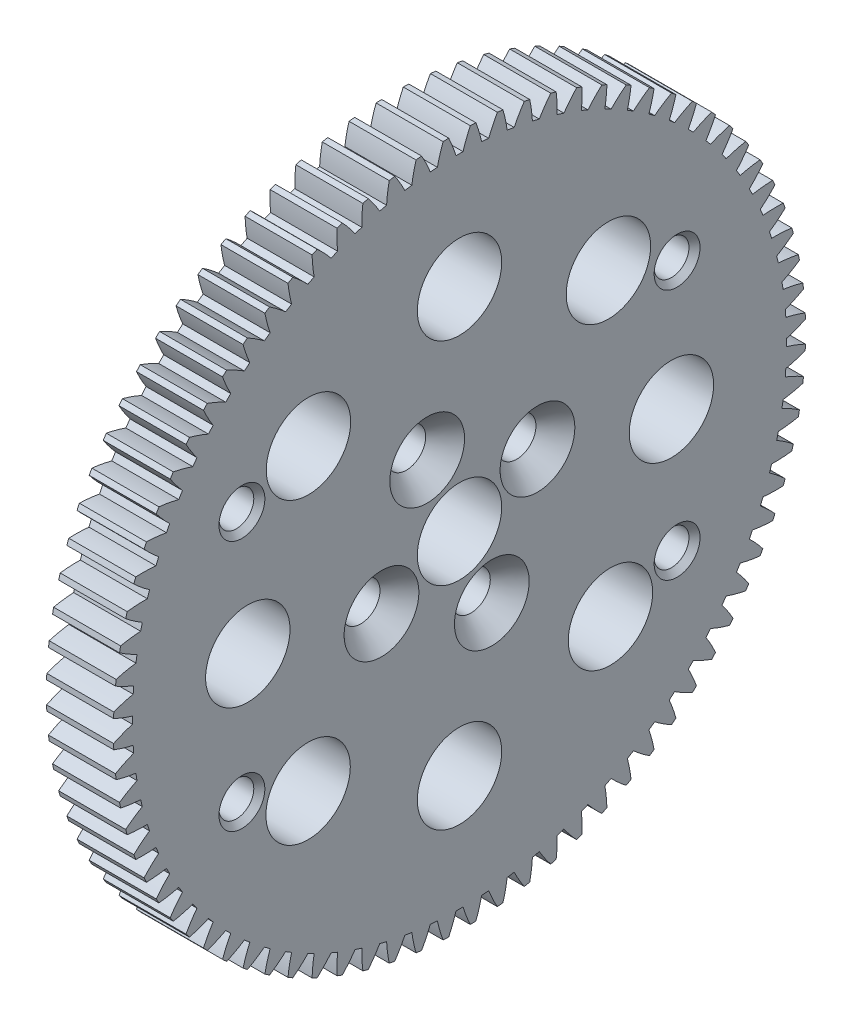
SolidWorks part; units mm, degrees
material "2024 Alloy"
ref_plane "Front Plane" through (0, 0, 0) normal (0, 0, 1) x (1, 0, 0)
ref_plane "Top Plane" through (0, 0, 0) normal (0, 1, 0) x (1, 0, 0)
ref_plane "Right Plane" through (0, 0, 0) normal (1, 0, 0) x (0, 0, -1)
ref_plane "Plane1" through (0, 0, 0) normal (-1, 0, 0) x (0, -1, 0)
ref_axis "Axis1" through (-3.4925, 0, 0) along (1, 0, 0)
sketch "Sketch1" plane through (0, 0, 0) normal (-1, 0, 0) x (0, -1, 0)
  line L0 (3.0615, 7.391) -> (-3.0615, -7.391) construction
  line L1 (7.391, -3.0615) -> (-7.391, 3.0615) construction
  circle A0 centre (0, 0) radius 4
  circle A1 centre (3.0615, 7.391) radius 1.75
  circle A2 centre (-20.084, 0) radius 4
  circle A3 centre (20.0633, 0) radius 4
  circle A4 centre (0, -20.084) radius 4
  circle A5 centre (0, 20.0633) radius 4
  circle A6 centre (-14.3663, -14.1126) radius 4
  circle A7 centre (14.142, -14.3069) radius 4
  circle A8 centre (14.1351, 14.3483) radius 4
  circle A9 centre (-14.1597, 14.315) radius 4
  circle A10 centre (-7.391, 3.0615) radius 1.75
  circle A11 centre (7.391, -3.0615) radius 1.75
  circle A12 centre (-3.0615, -7.391) radius 1.75
  arc A13 (-32.5405, -4.1179) -> (-30.6681, -4.5175) centre (-28.9403, 8.1654) ccw
  arc A14 (-30.6681, -4.5175) -> (-30.563, -5.1806) centre (0, 0) ccw
  arc A15 (-30.563, -5.1806) -> (-32.2203, -6.1392) centre (-25.0006, -16.7088) ccw
  arc A16 (-32.2203, -6.1392) -> (-32.1171, -6.6583) centre (0, 0) ccw
  arc A17 (-32.1171, -6.6583) -> (-30.2191, -6.9097) centre (-29.4917, 5.8696) ccw
  arc A18 (-30.2191, -6.9097) -> (-30.0624, -7.5626) centre (0, 0) ccw
  arc A19 (-30.0624, -7.5626) -> (-31.6393, -8.6483) centre (-23.6126, -18.6188) ccw
  arc A20 (-31.6393, -8.6483) -> (-31.4957, -9.1576) centre (0, 0) ccw
  arc A21 (-31.4957, -9.1576) -> (-29.5838, -9.2594) centre (-29.8613, 3.5376) ccw
  arc A22 (-29.5838, -9.2594) -> (-29.3763, -9.8979) centre (0, 0) ccw
  arc A23 (-29.3763, -9.8979) -> (-30.8633, -11.104) centre (-22.079, -20.414) ccw
  arc A24 (-30.8633, -11.104) -> (-30.6801, -11.6005) centre (0, 0) ccw
  arc A25 (-30.6801, -11.6005) -> (-28.7661, -11.552) centre (-30.0469, 1.1838) ccw
  arc A26 (-28.7661, -11.552) -> (-28.5092, -12.1723) centre (0, 0) ccw
  arc A27 (-28.5092, -12.1723) -> (-29.8969, -13.4913) centre (-20.4093, -22.0834) ccw
  arc A28 (-29.8969, -13.4913) -> (-29.6753, -13.9719) centre (0, 0) ccw
  arc A29 (-29.6753, -13.9719) -> (-27.7711, -13.7733) centre (-30.0471, -1.1773) ccw
  arc A30 (-27.7711, -13.7733) -> (-27.4663, -14.3715) centre (0, 0) ccw
  arc A31 (-27.4663, -14.3715) -> (-28.7462, -15.7954) centre (-18.6137, -23.6166) ccw
  arc A32 (-28.7462, -15.7954) -> (-28.4876, -16.2571) centre (0, 0) ccw
  arc A33 (-28.4876, -16.2571) -> (-26.6048, -15.9097) centre (-29.8621, -3.5311) ccw
  arc A34 (-26.6048, -15.9097) -> (-26.254, -16.4822) centre (0, 0) ccw
  arc A35 (-26.254, -16.4822) -> (-27.4183, -18.0021) centre (-16.7034, -25.0042) ccw
  arc A36 (-27.4183, -18.0021) -> (-27.1243, -18.4421) centre (0, 0) ccw
  arc A37 (-27.1243, -18.4421) -> (-25.2746, -17.9481) centre (-29.493, -5.8632) ccw
  arc A38 (-25.2746, -17.9481) -> (-24.8799, -18.4913) centre (0, 0) ccw
  arc A39 (-24.8799, -18.4913) -> (-25.9214, -20.0978) centre (-14.6901, -26.2377) ccw
  arc A40 (-25.9214, -20.0978) -> (-25.5937, -20.5134) centre (0, 0) ccw
  arc A41 (-25.5937, -20.5134) -> (-23.7885, -19.8758) centre (-28.9421, -8.1591) ccw
  arc A42 (-23.7885, -19.8758) -> (-23.3524, -20.3863) centre (0, 0) ccw
  arc A43 (-23.3524, -20.3863) -> (-24.2646, -22.0696) centre (-12.5862, -27.3094) ccw
  arc A44 (-24.2646, -22.0696) -> (-23.9054, -22.4582) centre (0, 0) ccw
  arc A45 (-23.9054, -22.4582) -> (-22.1557, -21.6809) centre (-28.2127, -10.4047) ccw
  arc A46 (-22.1557, -21.6809) -> (-21.6809, -22.1557) centre (0, 0) ccw
  arc A47 (-21.6809, -22.1557) -> (-22.4582, -23.9054) centre (-10.4047, -28.2127) ccw
  arc A48 (-22.4582, -23.9054) -> (-22.0696, -24.2646) centre (0, 0) ccw
  arc A49 (-22.0696, -24.2646) -> (-20.3863, -23.3524) centre (-27.3094, -12.5862) ccw
  arc A50 (-20.3863, -23.3524) -> (-19.8758, -23.7885) centre (0, 0) ccw
  arc A51 (-19.8758, -23.7885) -> (-20.5134, -25.5937) centre (-8.1591, -28.9421) ccw
  arc A52 (-20.5134, -25.5937) -> (-20.0978, -25.9214) centre (0, 0) ccw
  arc A53 (-20.0978, -25.9214) -> (-18.4913, -24.8799) centre (-26.2377, -14.6901) ccw
  arc A54 (-18.4913, -24.8799) -> (-17.9481, -25.2746) centre (0, 0) ccw
  arc A55 (-17.9481, -25.2746) -> (-18.4421, -27.1243) centre (-5.8632, -29.493) ccw
  arc A56 (-18.4421, -27.1243) -> (-18.0021, -27.4183) centre (0, 0) ccw
  arc A57 (-18.0021, -27.4183) -> (-16.4822, -26.254) centre (-25.0042, -16.7034) ccw
  arc A58 (-16.4822, -26.254) -> (-15.9097, -26.6048) centre (0, 0) ccw
  arc A59 (-15.9097, -26.6048) -> (-16.2571, -28.4876) centre (-3.5311, -29.8621) ccw
  arc A60 (-16.2571, -28.4876) -> (-15.7954, -28.7462) centre (0, 0) ccw
  arc A61 (-15.7954, -28.7462) -> (-14.3715, -27.4663) centre (-23.6166, -18.6137) ccw
  arc A62 (-14.3715, -27.4663) -> (-13.7733, -27.7711) centre (0, 0) ccw
  arc A63 (-13.7733, -27.7711) -> (-13.9719, -29.6753) centre (-1.1773, -30.0471) ccw
  arc A64 (-13.9719, -29.6753) -> (-13.4913, -29.8969) centre (0, 0) ccw
  arc A65 (-13.4913, -29.8969) -> (-12.1723, -28.5092) centre (-22.0834, -20.4093) ccw
  arc A66 (-12.1723, -28.5092) -> (-11.552, -28.7661) centre (0, 0) ccw
  arc A67 (-11.552, -28.7661) -> (-11.6005, -30.6801) centre (1.1838, -30.0469) ccw
  arc A68 (-11.6005, -30.6801) -> (-11.104, -30.8633) centre (0, 0) ccw
  arc A69 (-11.104, -30.8633) -> (-9.8979, -29.3763) centre (-20.414, -22.079) ccw
  arc A70 (-9.8979, -29.3763) -> (-9.2594, -29.5838) centre (0, 0) ccw
  arc A71 (-9.2594, -29.5838) -> (-9.1576, -31.4957) centre (3.5376, -29.8613) ccw
  arc A72 (-9.1576, -31.4957) -> (-8.6483, -31.6393) centre (0, 0) ccw
  arc A73 (-8.6483, -31.6393) -> (-7.5626, -30.0624) centre (-18.6188, -23.6126) ccw
  arc A74 (-7.5626, -30.0624) -> (-6.9097, -30.2191) centre (0, 0) ccw
  arc A75 (-6.9097, -30.2191) -> (-6.6583, -32.1171) centre (5.8696, -29.4917) ccw
  arc A76 (-6.6583, -32.1171) -> (-6.1392, -32.2203) centre (0, 0) ccw
  arc A77 (-6.1392, -32.2203) -> (-5.1806, -30.563) centre (-16.7088, -25.0006) ccw
  arc A78 (-5.1806, -30.563) -> (-4.5175, -30.6681) centre (0, 0) ccw
  arc A79 (-4.5175, -30.6681) -> (-4.1179, -32.5405) centre (8.1654, -28.9403) ccw
  arc A80 (-4.1179, -32.5405) -> (-3.5923, -32.6027) centre (0, 0) ccw
  arc A81 (-3.5923, -32.6027) -> (-2.7667, -30.8753) centre (-14.6958, -26.2345) ccw
  arc A82 (-2.7667, -30.8753) -> (-2.0973, -30.928) centre (0, 0) ccw
  arc A83 (-2.0973, -30.928) -> (-1.5521, -32.7633) centre (10.4109, -28.2104) ccw
  arc A84 (-1.5521, -32.7633) -> (-1.0233, -32.784) centre (0, 0) ccw
  arc A85 (-1.0233, -32.784) -> (-0.3357, -30.9972) centre (-12.5921, -27.3066) ccw
  arc A86 (-0.3357, -30.9972) -> (0.3357, -30.9972) centre (0, 0) ccw
  arc A87 (0.3357, -30.9972) -> (1.0233, -32.784) centre (12.5921, -27.3066) ccw
  arc A88 (1.0233, -32.784) -> (1.5521, -32.7633) centre (0, 0) ccw
  arc A89 (1.5521, -32.7633) -> (2.0973, -30.928) centre (-10.4109, -28.2104) ccw
  arc A90 (2.0973, -30.928) -> (2.7667, -30.8753) centre (0, 0) ccw
  arc A91 (2.7667, -30.8753) -> (3.5923, -32.6027) centre (14.6958, -26.2345) ccw
  arc A92 (3.5923, -32.6027) -> (4.1179, -32.5405) centre (0, 0) ccw
  arc A93 (4.1179, -32.5405) -> (4.5175, -30.6681) centre (-8.1654, -28.9403) ccw
  arc A94 (4.5175, -30.6681) -> (5.1806, -30.563) centre (0, 0) ccw
  arc A95 (5.1806, -30.563) -> (6.1392, -32.2203) centre (16.7088, -25.0006) ccw
  arc A96 (6.1392, -32.2203) -> (6.6583, -32.1171) centre (0, 0) ccw
  arc A97 (6.6583, -32.1171) -> (6.9097, -30.2191) centre (-5.8696, -29.4917) ccw
  arc A98 (6.9097, -30.2191) -> (7.5626, -30.0624) centre (0, 0) ccw
  arc A99 (7.5626, -30.0624) -> (8.6483, -31.6393) centre (18.6188, -23.6126) ccw
  arc A100 (8.6483, -31.6393) -> (9.1576, -31.4957) centre (0, 0) ccw
  arc A101 (9.1576, -31.4957) -> (9.2594, -29.5838) centre (-3.5376, -29.8613) ccw
  arc A102 (9.2594, -29.5838) -> (9.8979, -29.3763) centre (0, 0) ccw
  arc A103 (9.8979, -29.3763) -> (11.104, -30.8633) centre (20.414, -22.079) ccw
  arc A104 (11.104, -30.8633) -> (11.6005, -30.6801) centre (0, 0) ccw
  arc A105 (11.6005, -30.6801) -> (11.552, -28.7661) centre (-1.1838, -30.0469) ccw
  arc A106 (11.552, -28.7661) -> (12.1723, -28.5092) centre (0, 0) ccw
  arc A107 (12.1723, -28.5092) -> (13.4913, -29.8969) centre (22.0834, -20.4093) ccw
  arc A108 (13.4913, -29.8969) -> (13.9719, -29.6753) centre (0, 0) ccw
  arc A109 (13.9719, -29.6753) -> (13.7733, -27.7711) centre (1.1773, -30.0471) ccw
  arc A110 (13.7733, -27.7711) -> (14.3715, -27.4663) centre (0, 0) ccw
  arc A111 (14.3715, -27.4663) -> (15.7954, -28.7462) centre (23.6166, -18.6137) ccw
  arc A112 (15.7954, -28.7462) -> (16.2571, -28.4876) centre (0, 0) ccw
  arc A113 (16.2571, -28.4876) -> (15.9097, -26.6048) centre (3.5311, -29.8621) ccw
  arc A114 (15.9097, -26.6048) -> (16.4822, -26.254) centre (0, 0) ccw
  arc A115 (16.4822, -26.254) -> (18.0021, -27.4183) centre (25.0042, -16.7034) ccw
  arc A116 (18.0021, -27.4183) -> (18.4421, -27.1243) centre (0, 0) ccw
  arc A117 (18.4421, -27.1243) -> (17.9481, -25.2746) centre (5.8632, -29.493) ccw
  arc A118 (17.9481, -25.2746) -> (18.4913, -24.8799) centre (0, 0) ccw
  arc A119 (18.4913, -24.8799) -> (20.0978, -25.9214) centre (26.2377, -14.6901) ccw
  arc A120 (20.0978, -25.9214) -> (20.5134, -25.5937) centre (0, 0) ccw
  arc A121 (20.5134, -25.5937) -> (19.8758, -23.7885) centre (8.1591, -28.9421) ccw
  arc A122 (19.8758, -23.7885) -> (20.3863, -23.3524) centre (0, 0) ccw
  arc A123 (20.3863, -23.3524) -> (22.0696, -24.2646) centre (27.3094, -12.5862) ccw
  arc A124 (22.0696, -24.2646) -> (22.4582, -23.9054) centre (0, 0) ccw
  arc A125 (22.4582, -23.9054) -> (21.6809, -22.1557) centre (10.4047, -28.2127) ccw
  arc A126 (21.6809, -22.1557) -> (22.1557, -21.6809) centre (0, 0) ccw
  arc A127 (22.1557, -21.6809) -> (23.9054, -22.4582) centre (28.2127, -10.4047) ccw
  arc A128 (23.9054, -22.4582) -> (24.2646, -22.0696) centre (0, 0) ccw
  arc A129 (24.2646, -22.0696) -> (23.3524, -20.3863) centre (12.5862, -27.3094) ccw
  arc A130 (23.3524, -20.3863) -> (23.7885, -19.8758) centre (0, 0) ccw
  arc A131 (23.7885, -19.8758) -> (25.5937, -20.5134) centre (28.9421, -8.1591) ccw
  arc A132 (25.5937, -20.5134) -> (25.9214, -20.0978) centre (0, 0) ccw
  arc A133 (25.9214, -20.0978) -> (24.8799, -18.4913) centre (14.6901, -26.2377) ccw
  arc A134 (24.8799, -18.4913) -> (25.2746, -17.9481) centre (0, 0) ccw
  arc A135 (25.2746, -17.9481) -> (27.1243, -18.4421) centre (29.493, -5.8632) ccw
  arc A136 (27.1243, -18.4421) -> (27.4183, -18.0021) centre (0, 0) ccw
  arc A137 (27.4183, -18.0021) -> (26.254, -16.4822) centre (16.7034, -25.0042) ccw
  arc A138 (26.254, -16.4822) -> (26.6048, -15.9097) centre (0, 0) ccw
  arc A139 (26.6048, -15.9097) -> (28.4876, -16.2571) centre (29.8621, -3.5311) ccw
  arc A140 (28.4876, -16.2571) -> (28.7462, -15.7954) centre (0, 0) ccw
  arc A141 (28.7462, -15.7954) -> (27.4663, -14.3715) centre (18.6137, -23.6166) ccw
  arc A142 (27.4663, -14.3715) -> (27.7711, -13.7733) centre (0, 0) ccw
  arc A143 (27.7711, -13.7733) -> (29.6753, -13.9719) centre (30.0471, -1.1773) ccw
  arc A144 (29.6753, -13.9719) -> (29.8969, -13.4913) centre (0, 0) ccw
  arc A145 (29.8969, -13.4913) -> (28.5092, -12.1723) centre (20.4093, -22.0834) ccw
  arc A146 (28.5092, -12.1723) -> (28.7661, -11.552) centre (0, 0) ccw
  arc A147 (28.7661, -11.552) -> (30.6801, -11.6005) centre (30.0469, 1.1838) ccw
  arc A148 (30.6801, -11.6005) -> (30.8633, -11.104) centre (0, 0) ccw
  arc A149 (30.8633, -11.104) -> (29.3763, -9.8979) centre (22.079, -20.414) ccw
  arc A150 (29.3763, -9.8979) -> (29.5838, -9.2594) centre (0, 0) ccw
  arc A151 (29.5838, -9.2594) -> (31.4957, -9.1576) centre (29.8613, 3.5376) ccw
  arc A152 (31.4957, -9.1576) -> (31.6393, -8.6483) centre (0, 0) ccw
  arc A153 (31.6393, -8.6483) -> (30.0624, -7.5626) centre (23.6126, -18.6188) ccw
  arc A154 (30.0624, -7.5626) -> (30.2191, -6.9097) centre (0, 0) ccw
  arc A155 (30.2191, -6.9097) -> (32.1171, -6.6583) centre (29.4917, 5.8696) ccw
  arc A156 (32.1171, -6.6583) -> (32.2203, -6.1392) centre (0, 0) ccw
  arc A157 (32.2203, -6.1392) -> (30.563, -5.1806) centre (25.0006, -16.7088) ccw
  arc A158 (30.563, -5.1806) -> (30.6681, -4.5175) centre (0, 0) ccw
  arc A159 (30.6681, -4.5175) -> (32.5405, -4.1179) centre (28.9403, 8.1654) ccw
  arc A160 (32.5405, -4.1179) -> (32.6027, -3.5923) centre (0, 0) ccw
  arc A161 (32.6027, -3.5923) -> (30.8753, -2.7667) centre (26.2345, -14.6958) ccw
  arc A162 (30.8753, -2.7667) -> (30.928, -2.0973) centre (0, 0) ccw
  arc A163 (30.928, -2.0973) -> (32.7633, -1.5521) centre (28.2104, 10.4109) ccw
  arc A164 (32.7633, -1.5521) -> (32.784, -1.0233) centre (0, 0) ccw
  arc A165 (32.784, -1.0233) -> (30.9972, -0.3357) centre (27.3066, -12.5921) ccw
  arc A166 (30.9972, -0.3357) -> (30.9972, 0.3357) centre (0, 0) ccw
  arc A167 (30.9972, 0.3357) -> (32.784, 1.0233) centre (27.3066, 12.5921) ccw
  arc A168 (32.784, 1.0233) -> (32.7633, 1.5521) centre (0, 0) ccw
  arc A169 (32.7633, 1.5521) -> (30.928, 2.0973) centre (28.2104, -10.4109) ccw
  arc A170 (30.928, 2.0973) -> (30.8753, 2.7667) centre (0, 0) ccw
  arc A171 (30.8753, 2.7667) -> (32.6027, 3.5923) centre (26.2345, 14.6958) ccw
  arc A172 (32.6027, 3.5923) -> (32.5405, 4.1179) centre (0, 0) ccw
  arc A173 (32.5405, 4.1179) -> (30.6681, 4.5175) centre (28.9403, -8.1654) ccw
  arc A174 (30.6681, 4.5175) -> (30.563, 5.1806) centre (0, 0) ccw
  arc A175 (30.563, 5.1806) -> (32.2203, 6.1392) centre (25.0006, 16.7088) ccw
  arc A176 (32.2203, 6.1392) -> (32.1171, 6.6583) centre (0, 0) ccw
  arc A177 (32.1171, 6.6583) -> (30.2191, 6.9097) centre (29.4917, -5.8696) ccw
  arc A178 (30.2191, 6.9097) -> (30.0624, 7.5626) centre (0, 0) ccw
  arc A179 (30.0624, 7.5626) -> (31.6393, 8.6483) centre (23.6126, 18.6188) ccw
  arc A180 (31.6393, 8.6483) -> (31.4957, 9.1576) centre (0, 0) ccw
  arc A181 (31.4957, 9.1576) -> (29.5838, 9.2594) centre (29.8613, -3.5376) ccw
  arc A182 (29.5838, 9.2594) -> (29.3763, 9.8979) centre (0, 0) ccw
  arc A183 (29.3763, 9.8979) -> (30.8633, 11.104) centre (22.079, 20.414) ccw
  arc A184 (30.8633, 11.104) -> (30.6801, 11.6005) centre (0, 0) ccw
  arc A185 (30.6801, 11.6005) -> (28.7661, 11.552) centre (30.0469, -1.1838) ccw
  arc A186 (28.7661, 11.552) -> (28.5092, 12.1723) centre (0, 0) ccw
  arc A187 (28.5092, 12.1723) -> (29.8969, 13.4913) centre (20.4093, 22.0834) ccw
  arc A188 (29.8969, 13.4913) -> (29.6753, 13.9719) centre (0, 0) ccw
  arc A189 (29.6753, 13.9719) -> (27.7711, 13.7733) centre (30.0471, 1.1773) ccw
  arc A190 (27.7711, 13.7733) -> (27.4663, 14.3715) centre (0, 0) ccw
  arc A191 (27.4663, 14.3715) -> (28.7462, 15.7954) centre (18.6137, 23.6166) ccw
  arc A192 (28.7462, 15.7954) -> (28.4876, 16.2571) centre (0, 0) ccw
  arc A193 (28.4876, 16.2571) -> (26.6048, 15.9097) centre (29.8621, 3.5311) ccw
  arc A194 (26.6048, 15.9097) -> (26.254, 16.4822) centre (0, 0) ccw
  arc A195 (26.254, 16.4822) -> (27.4183, 18.0021) centre (16.7034, 25.0042) ccw
  arc A196 (27.4183, 18.0021) -> (27.1243, 18.4421) centre (0, 0) ccw
  arc A197 (27.1243, 18.4421) -> (25.2746, 17.9481) centre (29.493, 5.8632) ccw
  arc A198 (25.2746, 17.9481) -> (24.8799, 18.4913) centre (0, 0) ccw
  arc A199 (24.8799, 18.4913) -> (25.9214, 20.0978) centre (14.6901, 26.2377) ccw
  arc A200 (25.9214, 20.0978) -> (25.5937, 20.5134) centre (0, 0) ccw
  arc A201 (25.5937, 20.5134) -> (23.7885, 19.8758) centre (28.9421, 8.1591) ccw
  arc A202 (23.7885, 19.8758) -> (23.3524, 20.3863) centre (0, 0) ccw
  arc A203 (23.3524, 20.3863) -> (24.2646, 22.0696) centre (12.5862, 27.3094) ccw
  arc A204 (24.2646, 22.0696) -> (23.9054, 22.4582) centre (0, 0) ccw
  arc A205 (23.9054, 22.4582) -> (22.1557, 21.6809) centre (28.2127, 10.4047) ccw
  arc A206 (22.1557, 21.6809) -> (21.6809, 22.1557) centre (0, 0) ccw
  arc A207 (21.6809, 22.1557) -> (22.4582, 23.9054) centre (10.4047, 28.2127) ccw
  arc A208 (22.4582, 23.9054) -> (22.0696, 24.2646) centre (0, 0) ccw
  arc A209 (22.0696, 24.2646) -> (20.3863, 23.3524) centre (27.3094, 12.5862) ccw
  arc A210 (20.3863, 23.3524) -> (19.8758, 23.7885) centre (0, 0) ccw
  arc A211 (19.8758, 23.7885) -> (20.5134, 25.5937) centre (8.1591, 28.9421) ccw
  arc A212 (20.5134, 25.5937) -> (20.0978, 25.9214) centre (0, 0) ccw
  arc A213 (20.0978, 25.9214) -> (18.4913, 24.8799) centre (26.2377, 14.6901) ccw
  arc A214 (18.4913, 24.8799) -> (17.9481, 25.2746) centre (0, 0) ccw
  arc A215 (17.9481, 25.2746) -> (18.4421, 27.1243) centre (5.8632, 29.493) ccw
  arc A216 (18.4421, 27.1243) -> (18.0021, 27.4183) centre (0, 0) ccw
  arc A217 (18.0021, 27.4183) -> (16.4822, 26.254) centre (25.0042, 16.7034) ccw
  arc A218 (16.4822, 26.254) -> (15.9097, 26.6048) centre (0, 0) ccw
  arc A219 (15.9097, 26.6048) -> (16.2571, 28.4876) centre (3.5311, 29.8621) ccw
  arc A220 (16.2571, 28.4876) -> (15.7954, 28.7462) centre (0, 0) ccw
  arc A221 (15.7954, 28.7462) -> (14.3715, 27.4663) centre (23.6166, 18.6137) ccw
  arc A222 (14.3715, 27.4663) -> (13.7733, 27.7711) centre (0, 0) ccw
  arc A223 (13.7733, 27.7711) -> (13.9719, 29.6753) centre (1.1773, 30.0471) ccw
  arc A224 (13.9719, 29.6753) -> (13.4913, 29.8969) centre (0, 0) ccw
  arc A225 (13.4913, 29.8969) -> (12.1723, 28.5092) centre (22.0834, 20.4093) ccw
  arc A226 (12.1723, 28.5092) -> (11.552, 28.7661) centre (0, 0) ccw
  arc A227 (11.552, 28.7661) -> (11.6005, 30.6801) centre (-1.1838, 30.0469) ccw
  arc A228 (11.6005, 30.6801) -> (11.104, 30.8633) centre (0, 0) ccw
  arc A229 (11.104, 30.8633) -> (9.8979, 29.3763) centre (20.414, 22.079) ccw
  arc A230 (9.8979, 29.3763) -> (9.2594, 29.5838) centre (0, 0) ccw
  arc A231 (9.2594, 29.5838) -> (9.1576, 31.4957) centre (-3.5376, 29.8613) ccw
  arc A232 (9.1576, 31.4957) -> (8.6483, 31.6393) centre (0, 0) ccw
  arc A233 (8.6483, 31.6393) -> (7.5626, 30.0624) centre (18.6188, 23.6126) ccw
  arc A234 (7.5626, 30.0624) -> (6.9097, 30.2191) centre (0, 0) ccw
  arc A235 (6.9097, 30.2191) -> (6.6583, 32.1171) centre (-5.8696, 29.4917) ccw
  arc A236 (6.6583, 32.1171) -> (6.1392, 32.2203) centre (0, 0) ccw
  arc A237 (6.1392, 32.2203) -> (5.1806, 30.563) centre (16.7088, 25.0006) ccw
  arc A238 (5.1806, 30.563) -> (4.5175, 30.6681) centre (0, 0) ccw
  arc A239 (4.5175, 30.6681) -> (4.1179, 32.5405) centre (-8.1654, 28.9403) ccw
  arc A240 (4.1179, 32.5405) -> (3.5923, 32.6027) centre (0, 0) ccw
  arc A241 (3.5923, 32.6027) -> (2.7667, 30.8753) centre (14.6958, 26.2345) ccw
  arc A242 (2.7667, 30.8753) -> (2.0973, 30.928) centre (0, 0) ccw
  arc A243 (2.0973, 30.928) -> (1.5521, 32.7633) centre (-10.4109, 28.2104) ccw
  arc A244 (1.5521, 32.7633) -> (1.0233, 32.784) centre (0, 0) ccw
  arc A245 (1.0233, 32.784) -> (0.3357, 30.9972) centre (12.5921, 27.3066) ccw
  arc A246 (0.3357, 30.9972) -> (-0.3357, 30.9972) centre (0, 0) ccw
  arc A247 (-0.3357, 30.9972) -> (-1.0233, 32.784) centre (-12.5921, 27.3066) ccw
  arc A248 (-1.0233, 32.784) -> (-1.5521, 32.7633) centre (0, 0) ccw
  arc A249 (-1.5521, 32.7633) -> (-2.0973, 30.928) centre (10.4109, 28.2104) ccw
  arc A250 (-2.0973, 30.928) -> (-2.7667, 30.8753) centre (0, 0) ccw
  arc A251 (-2.7667, 30.8753) -> (-3.5923, 32.6027) centre (-14.6958, 26.2345) ccw
  arc A252 (-3.5923, 32.6027) -> (-4.1179, 32.5405) centre (0, 0) ccw
  arc A253 (-4.1179, 32.5405) -> (-4.5175, 30.6681) centre (8.1654, 28.9403) ccw
  arc A254 (-4.5175, 30.6681) -> (-5.1806, 30.563) centre (0, 0) ccw
  arc A255 (-5.1806, 30.563) -> (-6.1392, 32.2203) centre (-16.7088, 25.0006) ccw
  arc A256 (-6.1392, 32.2203) -> (-6.6583, 32.1171) centre (0, 0) ccw
  arc A257 (-6.6583, 32.1171) -> (-6.9097, 30.2191) centre (5.8696, 29.4917) ccw
  arc A258 (-6.9097, 30.2191) -> (-7.5626, 30.0624) centre (0, 0) ccw
  arc A259 (-7.5626, 30.0624) -> (-8.6483, 31.6393) centre (-18.6188, 23.6126) ccw
  arc A260 (-8.6483, 31.6393) -> (-9.1576, 31.4957) centre (0, 0) ccw
  arc A261 (-9.1576, 31.4957) -> (-9.2594, 29.5838) centre (3.5376, 29.8613) ccw
  arc A262 (-9.2594, 29.5838) -> (-9.8979, 29.3763) centre (0, 0) ccw
  arc A263 (-9.8979, 29.3763) -> (-11.104, 30.8633) centre (-20.414, 22.079) ccw
  arc A264 (-11.104, 30.8633) -> (-11.6005, 30.6801) centre (0, 0) ccw
  arc A265 (-11.6005, 30.6801) -> (-11.552, 28.7661) centre (1.1838, 30.0469) ccw
  arc A266 (-11.552, 28.7661) -> (-12.1723, 28.5092) centre (0, 0) ccw
  arc A267 (-12.1723, 28.5092) -> (-13.4913, 29.8969) centre (-22.0834, 20.4093) ccw
  arc A268 (-13.4913, 29.8969) -> (-13.9719, 29.6753) centre (0, 0) ccw
  arc A269 (-13.9719, 29.6753) -> (-13.7733, 27.7711) centre (-1.1773, 30.0471) ccw
  arc A270 (-13.7733, 27.7711) -> (-14.3715, 27.4663) centre (0, 0) ccw
  arc A271 (-14.3715, 27.4663) -> (-15.7954, 28.7462) centre (-23.6166, 18.6137) ccw
  arc A272 (-15.7954, 28.7462) -> (-16.2571, 28.4876) centre (0, 0) ccw
  arc A273 (-16.2571, 28.4876) -> (-15.9097, 26.6048) centre (-3.5311, 29.8621) ccw
  arc A274 (-15.9097, 26.6048) -> (-16.4822, 26.254) centre (0, 0) ccw
  arc A275 (-16.4822, 26.254) -> (-18.0021, 27.4183) centre (-25.0042, 16.7034) ccw
  arc A276 (-18.0021, 27.4183) -> (-18.4421, 27.1243) centre (0, 0) ccw
  arc A277 (-18.4421, 27.1243) -> (-17.9481, 25.2746) centre (-5.8632, 29.493) ccw
  arc A278 (-17.9481, 25.2746) -> (-18.4913, 24.8799) centre (0, 0) ccw
  arc A279 (-18.4913, 24.8799) -> (-20.0978, 25.9214) centre (-26.2377, 14.6901) ccw
  arc A280 (-20.0978, 25.9214) -> (-20.5134, 25.5937) centre (0, 0) ccw
  arc A281 (-20.5134, 25.5937) -> (-19.8758, 23.7885) centre (-8.1591, 28.9421) ccw
  arc A282 (-19.8758, 23.7885) -> (-20.3863, 23.3524) centre (0, 0) ccw
  arc A283 (-20.3863, 23.3524) -> (-22.0696, 24.2646) centre (-27.3094, 12.5862) ccw
  arc A284 (-22.0696, 24.2646) -> (-22.4582, 23.9054) centre (0, 0) ccw
  arc A285 (-22.4582, 23.9054) -> (-21.6809, 22.1557) centre (-10.4047, 28.2127) ccw
  arc A286 (-21.6809, 22.1557) -> (-22.1557, 21.6809) centre (0, 0) ccw
  arc A287 (-22.1557, 21.6809) -> (-23.9054, 22.4582) centre (-28.2127, 10.4047) ccw
  arc A288 (-23.9054, 22.4582) -> (-24.2646, 22.0696) centre (0, 0) ccw
  arc A289 (-24.2646, 22.0696) -> (-23.3524, 20.3863) centre (-12.5862, 27.3094) ccw
  arc A290 (-23.3524, 20.3863) -> (-23.7885, 19.8758) centre (0, 0) ccw
  arc A291 (-23.7885, 19.8758) -> (-25.5937, 20.5134) centre (-28.9421, 8.1591) ccw
  arc A292 (-25.5937, 20.5134) -> (-25.9214, 20.0978) centre (0, 0) ccw
  arc A293 (-25.9214, 20.0978) -> (-24.8799, 18.4913) centre (-14.6901, 26.2377) ccw
  arc A294 (-24.8799, 18.4913) -> (-25.2746, 17.9481) centre (0, 0) ccw
  arc A295 (-25.2746, 17.9481) -> (-27.1243, 18.4421) centre (-29.493, 5.8632) ccw
  arc A296 (-27.1243, 18.4421) -> (-27.4183, 18.0021) centre (0, 0) ccw
  arc A297 (-27.4183, 18.0021) -> (-26.254, 16.4822) centre (-16.7034, 25.0042) ccw
  arc A298 (-26.254, 16.4822) -> (-26.6048, 15.9097) centre (0, 0) ccw
  arc A299 (-26.6048, 15.9097) -> (-28.4876, 16.2571) centre (-29.8621, 3.5311) ccw
  arc A300 (-28.4876, 16.2571) -> (-28.7462, 15.7954) centre (0, 0) ccw
  arc A301 (-28.7462, 15.7954) -> (-27.4663, 14.3715) centre (-18.6137, 23.6166) ccw
  arc A302 (-27.4663, 14.3715) -> (-27.7711, 13.7733) centre (0, 0) ccw
  arc A303 (-27.7711, 13.7733) -> (-29.6753, 13.9719) centre (-30.0471, 1.1773) ccw
  arc A304 (-29.6753, 13.9719) -> (-29.8969, 13.4913) centre (0, 0) ccw
  arc A305 (-29.8969, 13.4913) -> (-28.5092, 12.1723) centre (-20.4093, 22.0834) ccw
  arc A306 (-28.5092, 12.1723) -> (-28.7661, 11.552) centre (0, 0) ccw
  arc A307 (-28.7661, 11.552) -> (-30.6801, 11.6005) centre (-30.0469, -1.1838) ccw
  arc A308 (-30.6801, 11.6005) -> (-30.8633, 11.104) centre (0, 0) ccw
  arc A309 (-30.8633, 11.104) -> (-29.3763, 9.8979) centre (-22.079, 20.414) ccw
  arc A310 (-29.3763, 9.8979) -> (-29.5838, 9.2594) centre (0, 0) ccw
  arc A311 (-29.5838, 9.2594) -> (-31.4957, 9.1576) centre (-29.8613, -3.5376) ccw
  arc A312 (-31.4957, 9.1576) -> (-31.6393, 8.6483) centre (0, 0) ccw
  arc A313 (-31.6393, 8.6483) -> (-30.0624, 7.5626) centre (-23.6126, 18.6188) ccw
  arc A314 (-30.0624, 7.5626) -> (-30.2191, 6.9097) centre (0, 0) ccw
  arc A315 (-30.2191, 6.9097) -> (-32.1171, 6.6583) centre (-29.4917, -5.8696) ccw
  arc A316 (-32.1171, 6.6583) -> (-32.2203, 6.1392) centre (0, 0) ccw
  arc A317 (-32.2203, 6.1392) -> (-30.563, 5.1806) centre (-25.0006, 16.7088) ccw
  arc A318 (-30.563, 5.1806) -> (-30.6681, 4.5175) centre (0, 0) ccw
  arc A319 (-30.6681, 4.5175) -> (-32.5405, 4.1179) centre (-28.9403, -8.1654) ccw
  arc A320 (-32.5405, 4.1179) -> (-32.6027, 3.5923) centre (0, 0) ccw
  arc A321 (-32.6027, 3.5923) -> (-30.8753, 2.7667) centre (-26.2345, 14.6958) ccw
  arc A322 (-30.8753, 2.7667) -> (-30.928, 2.0973) centre (0, 0) ccw
  arc A323 (-30.928, 2.0973) -> (-32.7633, 1.5521) centre (-28.2104, -10.4109) ccw
  arc A324 (-32.7633, 1.5521) -> (-32.784, 1.0233) centre (0, 0) ccw
  arc A325 (-32.784, 1.0233) -> (-30.9972, 0.3357) centre (-27.3066, 12.5921) ccw
  arc A326 (-30.9972, 0.3357) -> (-30.9972, -0.3357) centre (0, 0) ccw
  arc A327 (-30.9972, -0.3357) -> (-32.784, -1.0233) centre (-27.3066, -12.5921) ccw
  arc A328 (-32.784, -1.0233) -> (-32.7633, -1.5521) centre (0, 0) ccw
  arc A329 (-32.7633, -1.5521) -> (-30.928, -2.0973) centre (-28.2104, 10.4109) ccw
  arc A330 (-30.928, -2.0973) -> (-30.8753, -2.7667) centre (0, 0) ccw
  arc A331 (-30.8753, -2.7667) -> (-32.6027, -3.5923) centre (-26.2345, -14.6958) ccw
  arc A332 (-32.6027, -3.5923) -> (-32.5405, -4.1179) centre (0, 0) ccw
  point P506 (0, 0)
  point P507 (-2.286, -7.5626)
  dimension "D1" = 12.084
  dimension "D2" = 16
  dimension "D3" = 3.5
  dimension "D4" = 22.5
extrude "Boss-Extrude1" add sketch "Sketch1" against normal mid plane 6.35
sketch "Sketch2" plane through (0, 0, 0) normal (1, 0, 0) x (0, 0, -1)
  circle A0 centre (0, 0) radius 32 construction
  dimension "D1" = 64
sketch "Sketch3" plane through (0, 0, 0) normal (1, 0, 0) x (0, 0, -1)
  circle A6 centre (0, 23.8125) radius 1.9939
  circle A7 centre (-20.6222, 11.9063) radius 1.9939
  circle A8 centre (-20.6222, -11.9063) radius 1.9939
  circle A9 centre (0, -23.8125) radius 1.9939
  circle A10 centre (20.6222, -11.9063) radius 1.9939
  circle A11 centre (20.6222, 11.9063) radius 1.9939
hole_wizard "M4x0.7 Tapped Hole1" positions "Sketch4" profile "Sketch5" tap size "M4x0.7" standard "ANSI Metric" end condition through all
sketch "Sketch4" plane through (3.175, 0, 0) normal (1, 0, 0) x (0, 0, -1)
  point P0 (-20.6222, 11.9063)
  point P3 (-20.6222, -11.9063)
  point P6 (20.6222, 11.9063)
  point P9 (20.6222, -11.9063)
sketch "Sketch5" plane through (3.175, 11.9063, 20.6222) normal (0, 1, 0) x (0, 0, -1)
  line L0 (0, 0) -> (0, 6.35)
  line L1 (0, 6.35) -> (2.175, 6.35)
  line L2 (1.65, 5.825) -> (1.65, 0.525)
  line L3 (1.65, 0.525) -> (2.175, 0)
  line L5 (2.175, 0) -> (0, 0)
  line L6 (-1.65, 0.525) -> (-2.175, 0) construction
  line L7 (2.175, 6.35) -> (1.65, 5.825)
  line L8 (-2.175, 6.35) -> (-1.65, 5.825) construction
  line L11 (0, -6.35) -> (0, 107.95) construction
  dimension "Thread Major Dia." = 3.3
  dimension "Thru Tap Drill Depth" = 6.35
  dimension "Near C'Sink Dia." = 4.35
  dimension "Near C'Sink Angle" = 90
  dimension "Far C'Sink Dia." = 4.35
  dimension "Far C'Sink Angle" = 90
hole_wizard "CSK for #6 Flat Head Machine Screw1" positions "Sketch6" profile "Sketch7" countersink size "#6" standard "ANSI Inch" end condition through all
sketch "Sketch6" plane through (3.175, 0, 0) normal (1, 0, 0) x (0, 0, -1)
  point P0 (7.391, 3.0615)
  point P3 (3.0615, -7.391)
  point P6 (-7.391, -3.0615)
  point P9 (-3.0615, 7.391)
sketch "Sketch7" plane through (3.175, 3.0615, -7.391) normal (0, 1, 0) x (0, 0, -1)
  line L0 (0, 0) -> (0, 6.35)
  line L1 (0, 6.35) -> (1.8288, 6.35)
  line L2 (1.8288, 6.35) -> (1.8288, 1.9723)
  line L3 (1.8288, 1.9723) -> (3.5433, 0)
  line L5 (3.5433, 0) -> (0, 0)
  line L6 (-1.8288, 1.9723) -> (-3.5433, 0) construction
  line L11 (0, -6.35) -> (0, 107.95) construction
  dimension "Thru Hole Dia." = 3.6576
  dimension "Thru Hole Depth" = 6.35
  dimension "Near C'Sink Dia." = 7.0866
  dimension "Near C'Sink Angle" = 82
